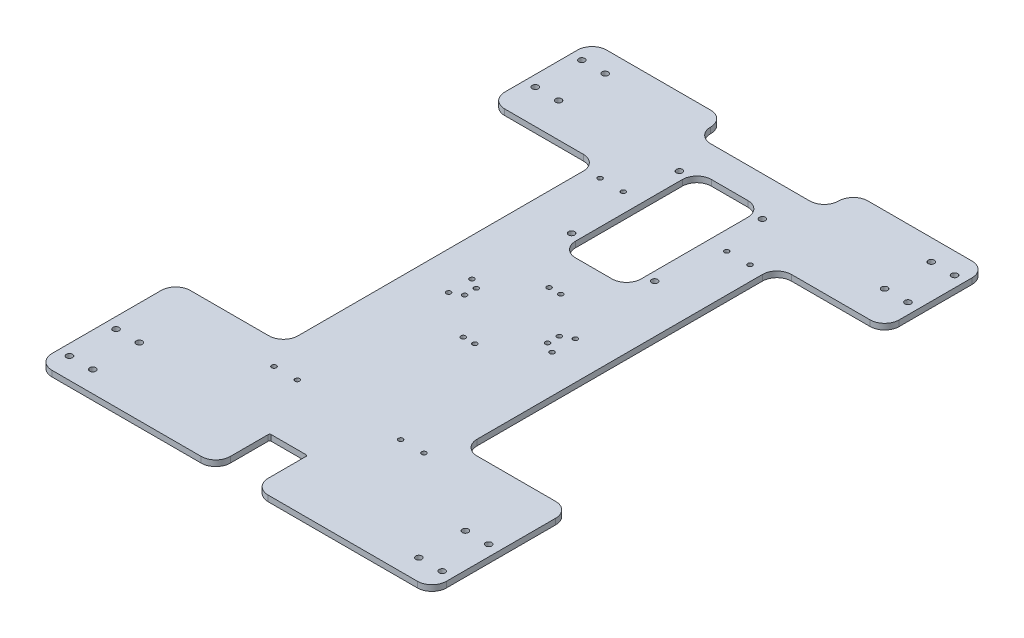
SolidWorks part; units mm, degrees
ref_plane "前视基准面" through (0, 0, 0) normal (0, 0, 1) x (1, 0, 0)
ref_plane "上视基准面" through (0, 0, 0) normal (0, 1, 0) x (1, 0, 0)
ref_plane "右视基准面" through (0, 0, 0) normal (1, 0, 0) x (0, 0, -1)
sketch "草图1" plane through (0, 0, 0) normal (0, 1, 0) x (1, 0, 0)
  line L1 (-135.5, 190.5) -> (135.5, 190.5)
  line L2 (-135.5, 190.5) -> (-135.5, -190.5)
  line L3 (-135.5, -190.5) -> (135.5, -190.5)
  line L4 (135.5, 190.5) -> (135.5, -190.5)
  line L5 (-135.5, 190.5) -> (135.5, -190.5) construction
  line L6 (-135.5, -190.5) -> (135.5, 190.5) construction
  point P0 (0, 0)
  dimension "D1" = 381
  dimension "D2" = 271
extrude "凸台-拉伸2" add sketch "草图1" along normal blind 4
sketch "草图4" plane through (0, 4, 0) normal (0, 1, 0) x (1, 0, 0)
  line L0 (-135.5, 0) -> (0, 0) construction
  line L1 (-135.5, 190.5) -> (-135.5, -190.5) construction
  line L2 (0, 0) -> (0, -190.5) construction
  line L3 (-135.5, -190.5) -> (135.5, -190.5) construction
  circle A0 centre (-128, -176) radius 2.1
  circle A1 centre (-128, -144) radius 2.1
  circle A2 centre (-112, -144) radius 2.1
  circle A3 centre (-112, -176) radius 2.1
  circle A4 centre (112, -144) radius 2.1
  circle A5 centre (128, -144) radius 2.1
  circle A6 centre (128, -176) radius 2.1
  circle A7 centre (112, -176) radius 2.1
  circle A8 centre (112, 176) radius 2.1
  circle A9 centre (128, 176) radius 2.1
  circle A10 centre (128, 144) radius 2.1
  circle A11 centre (112, 144) radius 2.1
  circle A12 centre (-112, 176) radius 2.1
  circle A13 centre (-112, 144) radius 2.1
  circle A14 centre (-128, 144) radius 2.1
  circle A15 centre (-128, 176) radius 2.1
  dimension "D1" = 7.5
  dimension "D2" = 16
  dimension "D4" = 4.2
  dimension "D3" = 32
  dimension "D5" = 14.5
extrude "切除-拉伸3" cut sketch "草图4" against normal blind 4
sketch "草图5" plane through (0, 4, 0) normal (0, 1, 0) x (1, 0, 0)
  line L0 (-135.5, -190.5) -> (135.5, -190.5) construction
  line L1 (-13, -227.55) -> (13, -227.55)
  line L2 (-13, -227.55) -> (-13, -153.45)
  line L3 (-13, -153.45) -> (13, -153.45)
  line L4 (13, -227.55) -> (13, -153.45)
  line L5 (-13, -227.55) -> (13, -153.45) construction
  line L6 (-13, -153.45) -> (13, -227.55) construction
  point P0 (0, -190.5)
  dimension "D1" = 74.1
  dimension "D2" = 26
extrude "切除-拉伸4" cut sketch "草图5" against normal blind 4
sketch "草图6" plane through (0, 4, 0) normal (0, 1, 0) x (1, 0, 0)
  line L0 (0, -153.45) -> (0, 190.5) construction
  line L1 (13, -153.45) -> (-13, -153.45) construction
  line L2 (135.5, 190.5) -> (-135.5, 190.5) construction
  line L3 (135.5, -190.5) -> (135.5, 190.5) construction
  line L4 (61.5, -95.5) -> (209.5, -95.5)
  line L5 (61.5, -95.5) -> (61.5, 120.5)
  line L6 (61.5, 120.5) -> (209.5, 120.5)
  line L7 (209.5, -95.5) -> (209.5, 120.5)
  line L8 (61.5, -95.5) -> (209.5, 120.5) construction
  line L9 (61.5, 120.5) -> (209.5, -95.5) construction
  line L10 (-61.5, -95.5) -> (-209.5, -95.5)
  line L11 (-61.5, 120.5) -> (-209.5, 120.5)
  line L12 (-61.5, -95.5) -> (-61.5, 120.5)
  line L13 (-209.5, 120.5) -> (-209.5, -95.5)
  point P6 (135.5, 12.5)
  dimension "D1" = 148
  dimension "D2" = 216
  dimension "D3" = 95.5
extrude "切除-拉伸6" cut sketch "草图6" against normal blind 4
sketch "草图7" plane through (0, 4, 0) normal (0, 1, 0) x (1, 0, 0)
  line L0 (0, 190.5) -> (0, -153.45) construction
  line L1 (135.5, 190.5) -> (-135.5, 190.5) construction
  line L2 (13, -153.45) -> (-13, -153.45) construction
  line L5 (-135.5, -95.5) -> (-135.5, -190.5) construction
  line L6 (0, 18.525) -> (116.5673, 18.525) construction
  line L7 (-135.5, -190.5) -> (-13, -190.5) construction
  circle A0 centre (-51.5, -112) radius 1.6
  circle A1 centre (-35.5, -112) radius 1.6
  circle A2 centre (35.5, -112) radius 1.6
  circle A3 centre (51.5, -112) radius 1.6
  dimension "D1" = 3.2
  dimension "D3" = 84
  dimension "D2" = 78.5
  dimension "D4" = 16
extrude "切除-拉伸7" cut sketch "草图7" against normal blind 4
sketch "草图8" plane through (0, 4, 0) normal (0, 1, 0) x (1, 0, 0)
  line L0 (0, 190.5) -> (0, -153.45) construction
  line L1 (135.5, 190.5) -> (-135.5, 190.5) construction
  line L2 (13, -153.45) -> (-13, -153.45) construction
  line L3 (-135.5, 190.5) -> (-135.5, 120.5) construction
  circle A1 centre (-35.5, 8) radius 1.6
  circle A3 centre (-35.5, -8) radius 1.6
  circle A4 centre (35.5, -8) radius 1.6
  circle A6 centre (35.5, 8) radius 1.6
  dimension "D2" = 182.5
  dimension "D3" = 3.2
  dimension "D1" = 100
  dimension "D4" = 16
extrude "切除-拉伸8" cut sketch "草图8" against normal blind 4
sketch "草图9" plane through (0, 4, 0) normal (0, 1, 0) x (1, 0, 0)
  line L0 (0, 190.5) -> (0, -153.45) construction
  line L1 (135.5, 190.5) -> (-135.5, 190.5) construction
  line L2 (13, -153.45) -> (-13, -153.45) construction
  line L3 (-135.5, -190.5) -> (-13, -190.5) construction
  line L4 (-22.5, 149.5) -> (22.5, 149.5)
  line L5 (-22.5, 149.5) -> (-22.5, 56.2)
  line L6 (-22.5, 56.2) -> (22.5, 56.2)
  line L7 (22.5, 149.5) -> (22.5, 56.2)
  line L8 (-22.5, 149.5) -> (22.5, 56.2) construction
  line L9 (-22.5, 56.2) -> (22.5, 149.5) construction
  point P6 (0, 102.85)
  dimension "D1" = 246.7
  dimension "D2" = 93.3
  dimension "D3" = 45
extrude "切除-拉伸9" cut sketch "草图9" against normal blind 4
sketch "草图10" plane through (0, 4, 0) normal (0, 1, 0) x (1, 0, 0)
  line L0 (0, 190.5) -> (0, 0) construction
  line L1 (135.5, 190.5) -> (-135.5, 190.5) construction
  line L2 (-22.5, 149.5) -> (-22.5, 56.2) construction
  circle A0 centre (-28.5, 69.5) radius 2.1
  circle A1 centre (28.5, 69.5) radius 2.1
  dimension "D1" = 6
  dimension "D2" = 4.2
  dimension "D3" = 121
extrude "切除-拉伸10" cut sketch "草图10" against normal blind 4
sketch "草图11" plane through (0, 4, 0) normal (0, 1, 0) x (1, 0, 0)
  line L0 (0, 190.5) -> (0, -153.45) construction
  line L1 (135.5, 190.5) -> (-135.5, 190.5) construction
  line L2 (13, -153.45) -> (-13, -153.45) construction
  line L3 (-22.5, 149.5) -> (-22.5, 56.2) construction
  circle A0 centre (-51.5, 112) radius 1.6
  circle A1 centre (-35.5, 112) radius 1.6
  circle A2 centre (35.5, 112) radius 1.6
  circle A3 centre (51.5, 112) radius 1.6
  dimension "D1" = 3.2
  dimension "D2" = 16
  dimension "D3" = 78.5
  dimension "D4" = 13
extrude "切除-拉伸11" cut sketch "草图11" against normal blind 4
sketch "草图12" plane through (0, 4, 0) normal (0, 1, 0) x (1, 0, 0)
  line L0 (0, 190.5) -> (0, 39.3109) construction
  line L1 (135.5, 190.5) -> (-135.5, 190.5) construction
  line L2 (-22.5, 149.5) -> (-22.5, 56.2) construction
  circle A0 centre (-28.5, 143.5) radius 2.1
  circle A1 centre (28.5, 143.5) radius 2.1
  dimension "D1" = 4.2
  dimension "D2" = 47
  dimension "D3" = 6
extrude "切除-拉伸12" cut sketch "草图12" against normal blind 4
sketch "草图13" plane through (0, 4, 0) normal (0, 1, 0) x (1, 0, 0)
  line L0 (135.5, 190.5) -> (-135.5, 190.5) construction
  line L1 (-44, 210.5) -> (44, 210.5)
  line L2 (-44, 210.5) -> (-44, 170.5)
  line L3 (-44, 170.5) -> (44, 170.5)
  line L4 (44, 210.5) -> (44, 170.5)
  line L5 (-44, 210.5) -> (44, 170.5) construction
  line L6 (-44, 170.5) -> (44, 210.5) construction
  point P0 (0, 190.5)
  dimension "D1" = 40
  dimension "D2" = 88
extrude "切除-拉伸13" cut sketch "草图13" against normal blind 4
fillet "圆角3" radius 10 4 edges at (22.5, 2, -56.2) (-22.5, 2, -56.2) (22.5, 2, -149.5) (-22.5, 2, -149.5)
fillet "圆角5" radius 10 18 edges at (-44, 2, -170.5) (-44, 2, -190.5) (-135.5, 2, -190.5) (-135.5, 2, -120.5) (-61.5, 2, -120.5) (-61.5, 2, 95.5) (-135.5, 2, 95.5) (-135.5, 2, 190.5) (-13, 2, 190.5) (13, 2, 190.5) (135.5, 2, 190.5) (135.5, 2, 95.5) (61.5, 2, 95.5) (61.5, 2, -120.5) (135.5, 2, -120.5) (135.5, 2, -190.5) (44, 2, -190.5) (44, 2, -170.5)
fillet "圆角6" radius 1 2 edges at (13, 2, 153.45) (-13, 2, 153.45)
sketch "草图15" plane through (0, 4, 0) normal (0, 1, 0) x (1, 0, 0)
  line L0 (0, 0) -> (-85.5799, 0) construction
  line L5 (0, 0) -> (0, -35.4719) construction
  line L7 (0, 0) -> (0, 44.5306) construction
  line L8 (-135.5, -105.5) -> (-135.5, -180.5) construction
  circle A4 centre (-28.5, -4) radius 1.6
  circle A5 centre (-28.5, 4) radius 1.6
  circle A8 centre (-4, 29.5) radius 1.6
  circle A9 centre (-35.5, -8) radius 1.6 construction
  circle A11 centre (28.5, 4) radius 1.6
  circle A12 centre (28.5, -4) radius 1.6
  circle A13 centre (4, 29.5) radius 1.6
  circle A14 centre (4, -29.5) radius 1.6
  circle A15 centre (-4, -29.5) radius 1.6
  point P0 (0, 0)
  dimension "D3" = 3.2
  dimension "D4" = 3.2
  dimension "D5" = 48.95
  dimension "D6" = 29.5
  dimension "D7" = 4
  dimension "D8" = 4
  dimension "D1" = 8
  dimension "D2" = 28.5
extrude "切除-拉伸17" cut sketch "草图15" against normal blind 10
